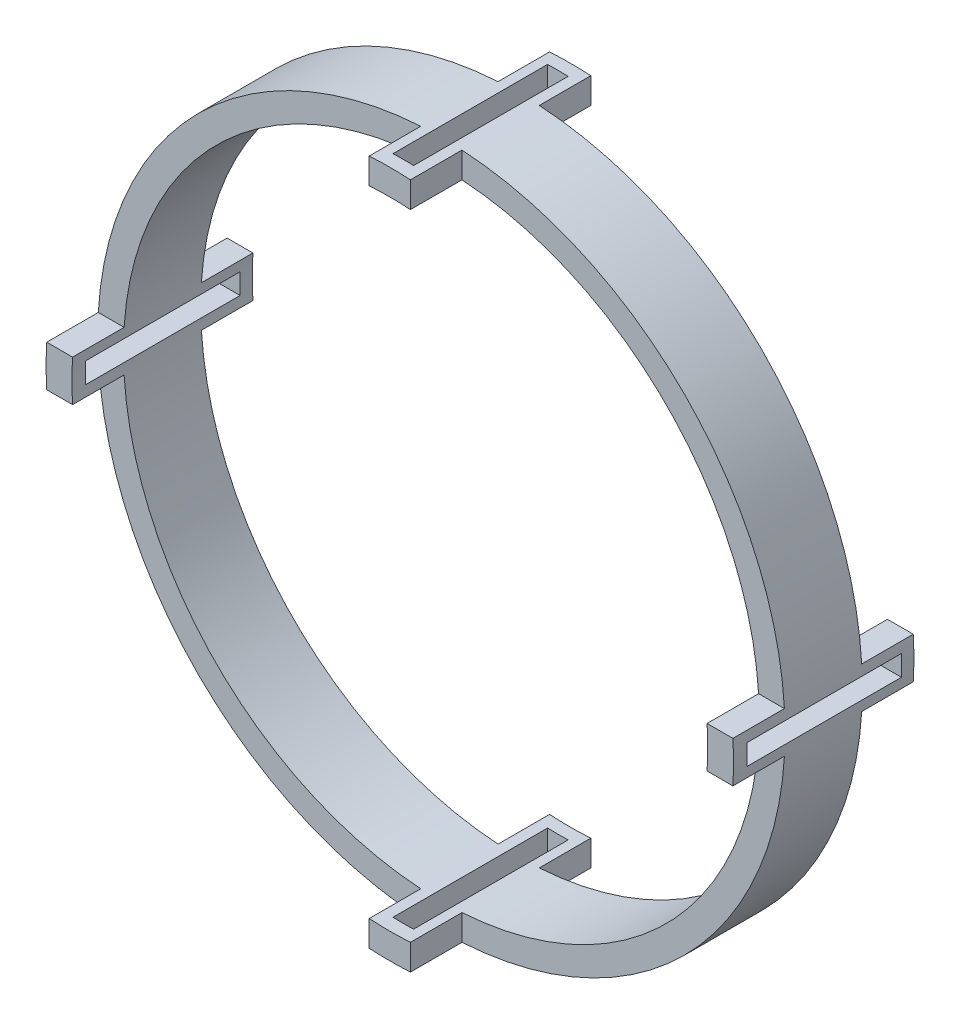
SolidWorks part; units mm, degrees
ref_plane "Front Plane" through (0, 0, 0) normal (0, 0, 1) x (1, 0, 0)
ref_plane "Top Plane" through (0, 0, 0) normal (0, 1, 0) x (1, 0, 0)
ref_plane "Right Plane" through (0, 0, 0) normal (1, 0, 0) x (0, 0, -1)
sketch "Sketch1" plane through (0, 0, 0) normal (0, 0, 1) x (1, 0, 0)
  circle A0 centre (0, 0) radius 78.359
  circle A1 centre (0, 0) radius 84.709
  dimension "D1" = 156.718
  dimension "D2" = 169.418
extrude "Boss-Extrude1" add sketch "Sketch1" along normal blind 19.05
sketch "Sketch3" plane through (0, 0, 0) normal (0, 0, -1) x (-1, 0, 0)
  line L0 (30.8173, 0) -> (-22.3005, 0) construction
  line L1 (0, -12.9993) -> (0, 95.4691) construction
  line L2 (-5.08, 78.1942) -> (-5.08, 84.5565)
  line L3 (5.08, 78.1942) -> (5.08, 84.5565)
  line L4 (-5.08, -78.1942) -> (-5.08, -84.5565)
  line L5 (5.08, -78.1942) -> (5.08, -84.5565)
  line L6 (0, 0) -> (44.2484, -44.2484) construction
  line L7 (78.1942, -5.08) -> (84.5565, -5.08)
  line L8 (78.1942, 5.08) -> (84.5565, 5.08)
  line L9 (-78.1942, 5.08) -> (-84.5565, 5.08)
  line L10 (-78.1942, -5.08) -> (-84.5565, -5.08)
  arc A0 (5.08, 78.1942) -> (-5.08, 78.1942) centre (0, 0) ccw
  circle A2 centre (0, 0) radius 78.359 construction
  arc A3 (5.08, 84.5565) -> (-5.08, 84.5565) centre (0, 0) ccw
  circle A4 centre (0, 0) radius 84.709 construction
  arc A5 (5.08, -78.1942) -> (-5.08, -78.1942) centre (0, 0) cw
  arc A6 (5.08, -84.5565) -> (-5.08, -84.5565) centre (0, 0) cw
  arc A7 (84.5565, -5.08) -> (84.5565, 5.08) centre (0, 0) ccw
  arc A8 (78.1942, -5.08) -> (78.1942, 5.08) centre (0, 0) ccw
  arc A9 (-78.1942, -5.08) -> (-78.1942, 5.08) centre (0, 0) cw
  arc A10 (-84.5565, -5.08) -> (-84.5565, 5.08) centre (0, 0) cw
  dimension "D1" = 5.08
  dimension "D2" = 5.08
  dimension "D3" = 5.08
  dimension "D4" = 5.08
  dimension "D5" = 45
extrude "Boss-Extrude2" add sketch "Sketch3" along normal blind 12.7 and the other way blind 31.75
sketch "Sketch2" plane through (0, 0, 0) normal (0, 1, 0) x (1, 0, 0)
  line L1 (0, -2.0807) -> (0, -15.8358) construction
  line L3 (-2.54, -28.4318) -> (2.54, -28.4318)
  line L4 (-2.54, -28.4318) -> (-2.54, 9.6682)
  line L5 (-2.54, 9.6682) -> (2.54, 9.6682)
  line L6 (2.54, -28.4318) -> (2.54, 9.6682)
  line L7 (-2.54, -28.4318) -> (2.54, 9.6682) construction
  line L8 (-2.54, 9.6682) -> (2.54, -28.4318) construction
  point P0 (0, -9.3818)
  dimension "D1" = 5.08
  dimension "D2" = 38.1
ref_axis "Axis1" through (0, 0, 2.0807) along (0, 0, 1)
extrude "Cut-Extrude1" cut sketch "Sketch2" against normal through all
pattern_circular "CirPattern1" count 4 over 360 about axis through (0, 0, 2.0807) along (0, 0, 1) of "Cut-Extrude1"
